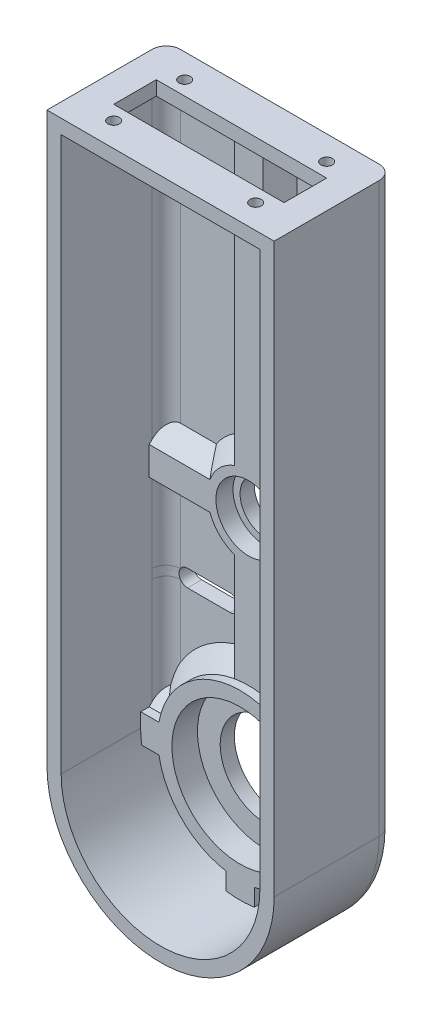
SolidWorks part; units mm, degrees
ref_plane "Plano frontal" through (0, 0, 0) normal (0, 0, 1) x (1, 0, 0)
ref_plane "Plano superior" through (0, 0, 0) normal (0, 1, 0) x (1, 0, 0)
ref_plane "Plano direito" through (0, 0, 0) normal (1, 0, 0) x (0, 0, -1)
sketch "Esboço1" plane through (0, 0, 0) normal (0, 0, 1) x (1, 0, 0)
  line L1 (-40, -100) -> (40, -100) construction
  line L2 (-40, -100) -> (-40, 100)
  line L3 (-40, 100) -> (40, 100)
  line L4 (40, -100) -> (40, 100)
  line L5 (-40, -100) -> (40, 100) construction
  line L6 (-40, 100) -> (40, -100) construction
  arc A0 (-40, -100) -> (40, -100) centre (0, -100) ccw
  circle A1 centre (0, -100) radius 16
  point P0 (0, 0)
  dimension "D3" = 32
  dimension "D1" = 80
  dimension "D2" = 200
extrude "Ressalto-extrusão1" add sketch "Esboço1" along normal blind 42
shell "Casca1" thickness 5 removed face at (0, -10, 42) removed face at (16, -100, 42)
sketch "Esboço3" plane through (0, 100, 0) normal (0, 1, 0) x (1, 0, 0)
  line L0 (0, -42) -> (0, 0) construction
  line L1 (40, -42) -> (-40, -42) construction
  line L2 (40, 0) -> (-40, 0) construction
  line L3 (40, -21) -> (-40, -21) construction
  line L4 (40, -42) -> (40, 0) construction
  line L5 (-40, -42) -> (-40, 0) construction
  line L7 (30, -13.5) -> (-30, -13.5)
  line L8 (30, -13.5) -> (30, -28.5)
  line L9 (30, -28.5) -> (-30, -28.5)
  line L10 (-30, -13.5) -> (-30, -28.5)
  line L11 (30, -13.5) -> (-30, -28.5) construction
  line L12 (30, -28.5) -> (-30, -13.5) construction
  line L13 (25, -8.5) -> (-25, -8.5) construction
  line L14 (25, -8.5) -> (25, -33.5) construction
  line L15 (25, -33.5) -> (-25, -33.5) construction
  line L16 (-25, -8.5) -> (-25, -33.5) construction
  line L17 (25, -8.5) -> (-25, -33.5) construction
  line L18 (25, -33.5) -> (-25, -8.5) construction
  circle A0 centre (25, -33.5) radius 2
  circle A1 centre (-25, -33.5) radius 2
  circle A2 centre (-25, -8.5) radius 2
  circle A3 centre (25, -8.5) radius 2
  point P12 (0, -21)
  point P17 (0, -21)
  dimension "D5" = 4
  dimension "D1" = 60
  dimension "D2" = 15
  dimension "D3" = 50
  dimension "D4" = 25
extrude "Corte-extrusão1" cut sketch "Esboço3" against normal up to surface (5 mm away) up to face at (0, 95, 23.5)
sketch "Esboço4" plane through (0, 0, 5) normal (0, 0, 1) x (1, 0, 0)
  circle A0 centre (0, -100) radius 24
  circle A1 centre (0, -100) radius 29
  dimension "D1" = 48
  dimension "D2" = 58
extrude "Ressalto-extrusão2" add sketch "Esboço4" along normal blind 9
sketch "Esboço5" plane through (0, 0, 5) normal (0, 0, 1) x (1, 0, 0)
  circle A0 centre (0, -20) radius 9
  circle A1 centre (0, -100) radius 16 construction
  dimension "D1" = 80
  dimension "D2" = 18
extrude "Corte-extrusão2" cut sketch "Esboço5" against normal up to surface (5 mm away) up to face at (0, -10, 0)
sketch "Esboço6" plane through (0, 0, 5) normal (0, 0, 1) x (1, 0, 0)
  circle A0 centre (0, -20) radius 11.5
  circle A1 centre (0, -20) radius 14.5
  dimension "D1" = 23
  dimension "D2" = 29
extrude "Ressalto-extrusão3" add sketch "Esboço6" along normal blind 6
sketch "Esboço7" plane through (0, 0, 14) normal (0, 0, 1) x (1, 0, 0)
  line L0 (29, -100) -> (35, -100)
  line L1 (-29, -100) -> (-35, -100)
  line L2 (0, -129) -> (0, -135)
  circle A0 centre (0, -100) radius 29 construction
  circle A1 centre (0, -100) radius 29 construction
  arc A2 (-35, -100) -> (35, -100) centre (0, -100) ccw construction
rib "Nervura1" sketch "Esboço7" sketch "Esboço7" thickness 10 extrusion direction normal to sketch draft on no parameters "D1"=10
sketch "Esboço8" plane through (0, 0, 11) normal (0, 0, 1) x (1, 0, 0)
  line L0 (14.5, -20) -> (35, -20)
  line L1 (35, -95) -> (35, 95) construction
  line L2 (-14.5, -20) -> (-35, -20)
  line L3 (-35, 95) -> (-35, -100) construction
  line L4 (0, -5.5) -> (0, 95)
  line L5 (35, 95) -> (-35, 95) construction
  line L6 (0, -34.5) -> (0, -71)
  circle A0 centre (0, -20) radius 14.5 construction
  circle A1 centre (0, -20) radius 14.5 construction
  arc A2 (28.5657, -95) -> (-28.5657, -95) centre (0, -100) ccw construction
rib "Nervura2" sketch "Esboço8" sketch "Esboço8" thickness 10 extrusion direction normal to sketch draft on no parameters "D1"=10
sketch "Esboço9" plane through (0, 0, 5) normal (0, 0, 1) x (1, 0, 0)
  line L0 (-27.5, -55) -> (-12.5, -55) construction
  line L1 (-27.5, -52) -> (-12.5, -52)
  line L2 (-27.5, -58) -> (-12.5, -58)
  line L3 (-40, 100) -> (-40, -100) construction
  line L4 (0, -100) -> (0, -84) construction
  arc A0 (-27.5, -52) -> (-27.5, -58) centre (-27.5, -55) ccw
  arc A1 (-12.5, -58) -> (-12.5, -52) centre (-12.5, -55) ccw
  circle A2 centre (0, -100) radius 16 construction
  point P2 (-20, -55)
  dimension "D2" = 3
  dimension "D1" = 20
  dimension "D3" = 15
  dimension "D4" = 45
extrude "Corte-extrusão3" cut sketch "Esboço9" against normal up to surface (5 mm away) up to face at (16, -100, 0)
sketch "Esboço10" plane through (0, 0, 5) normal (0, 0, 1) x (1, 0, 0)
  line L0 (0, -100) -> (35, -45.2277) construction
  line L2 (35, -95) -> (35, -25) construction
  line L3 (0, -100) -> (35, -51.266) construction
  line L7 (14.6835, -56.3488) -> (22.2163, -49.7717)
  line L8 (21.5385, -66.294) -> (28.6945, -60.0457) construction
  line L9 (22.2163, -49.7717) -> (19.5854, -46.7586)
  line L10 (19.5854, -46.7586) -> (12.0527, -53.3357)
  line L11 (12.0527, -53.3357) -> (14.6835, -56.3488)
  circle A0 centre (21.5385, -66.294) radius 1.2
  circle A1 centre (28.6945, -60.0457) radius 1.2
  dimension "D1" = 9.5
  dimension "D2" = 2.4
  dimension "D3" = 40
  dimension "D4" = 65
  dimension "D5" = 60
  dimension "D6" = 10
  dimension "D7" = 12
  dimension "D8" = 4
extrude "Corte-extrusão4" cut sketch "Esboço10" against normal up to surface (5 mm away) up to face at (-20, -55, 0)
ref_plane "Plano1" through (0, -65, 0) normal (0, -1, 0) x (-1, 0, 0)
sketch "Esboço11" plane through (0, -65, 0) normal (0, -1, 0) x (-1, 0, 0)
  line L0 (-40, -21) -> (-31, -21)
  line L1 (-40, -42) -> (-40, 0) construction
  line L2 (-31, -21) -> (-31, -36)
  line L3 (-31, -36) -> (-33, -36)
  line L4 (-33, -36) -> (-33, -26)
  line L5 (-33, -26) -> (-40, -26)
  line L6 (-40, -26) -> (-40, -21)
  dimension "D1" = 9
  dimension "D2" = 7
  dimension "D3" = 15
  dimension "D4" = 10
extrude "Ressalto-extrusão4" add sketch "Esboço11" along normal blind 4
fillet "Filete1" radius 1.5 3 edges at (31, -67, 21) (31, -67, 36) (33, -67, 36)
pattern_linear "Padrão linear1" count 3 spacing 65 along (0, 1, 0) of "Filete1", "Ressalto-extrusão4"
chamfer "Chanfro1" distance 6 angle 45 22 edges at (-31.6034, -105, 5) (5, -131.6034, 5) (-5, -131.6034, 5) (31.6034, -105, 5) (-20.5061, -120.5061, 5) (20.5061, -120.5061, 5) (20.5061, -79.4939, 5) (-20.5061, -79.4939, 5) (31.7829, -95, 5) (24.3053, -25, 5) (5, -52.5225, 5) (-10.253, -30.253, 5) (10.253, -30.253, 5) (-10.253, -9.747, 5) (10.253, -9.747, 5) (-31.7829, -95, 5) (-5, -52.5225, 5) (-24.3053, -25, 5) (24.3053, -15, 5) (5, 44.3053, 5) (-24.3053, -15, 5) (-5, 44.3053, 5)
fillet "Filete2" radius 5 4 edges at (35, -60, 5) (-35, -60, 5) (-35, 43, 5) (35, 43, 5)
fillet "Filete3" radius 5 3 edges at (-40, 0, 0) (0, -140, 0) (40, 0, 0)
